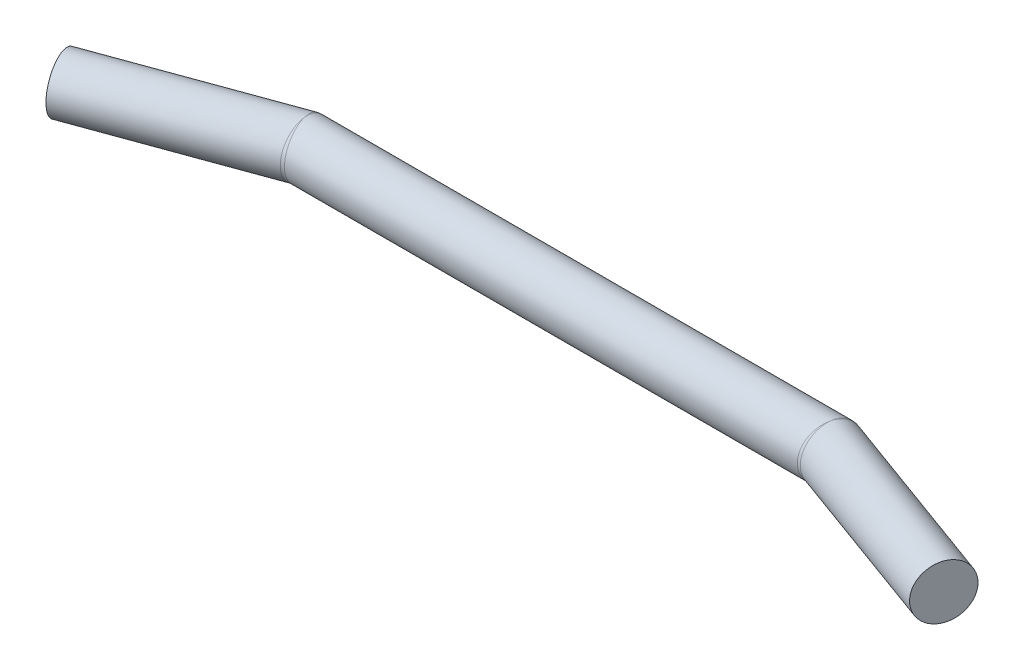
SolidWorks part; units mm, degrees
material "1060 Alloy"
ref_plane "Front Plane" through (0, 0, 0) normal (0, 0, 1) x (1, 0, 0)
ref_plane "Top Plane" through (0, 0, 0) normal (0, 1, 0) x (1, 0, 0)
ref_plane "Right Plane" through (0, 0, 0) normal (1, 0, 0) x (0, 0, -1)
sketch "Sketch1" plane through (0, 0, 0) normal (1, 0, 0) x (0, 0, -1)
  circle A0 centre (0, 0) radius 12.7
  dimension "D1" = 25.4
sketch "Bar Shape (CHANGE ANGLE HERE)" plane through (0, 0, 0) normal (0, 1, 0) x (1, 0, 0)
  line L0 (-125, 0) -> (125, 0)
  line L1 (0, 25) -> (0, -25) construction
  line L2 (-125, 0) -> (-209.5723, -30.7818)
  line L3 (125, 0) -> (209.5723, -30.7818)
  point P4 (0, 0)
  point P8 (0, 0)
  dimension "D1" = 250
  dimension "D2" = 90
  dimension "D3" = 50
  dimension "D4" = 160
sweep "Sweep1" add profiles "Sketch1" path "Bar Shape (CHANGE ANGLE HERE)"
fillet "Fillet1" radius 5 2 edges at (127.2394, 0, -12.7) (-127.2394, 0, -12.7)
